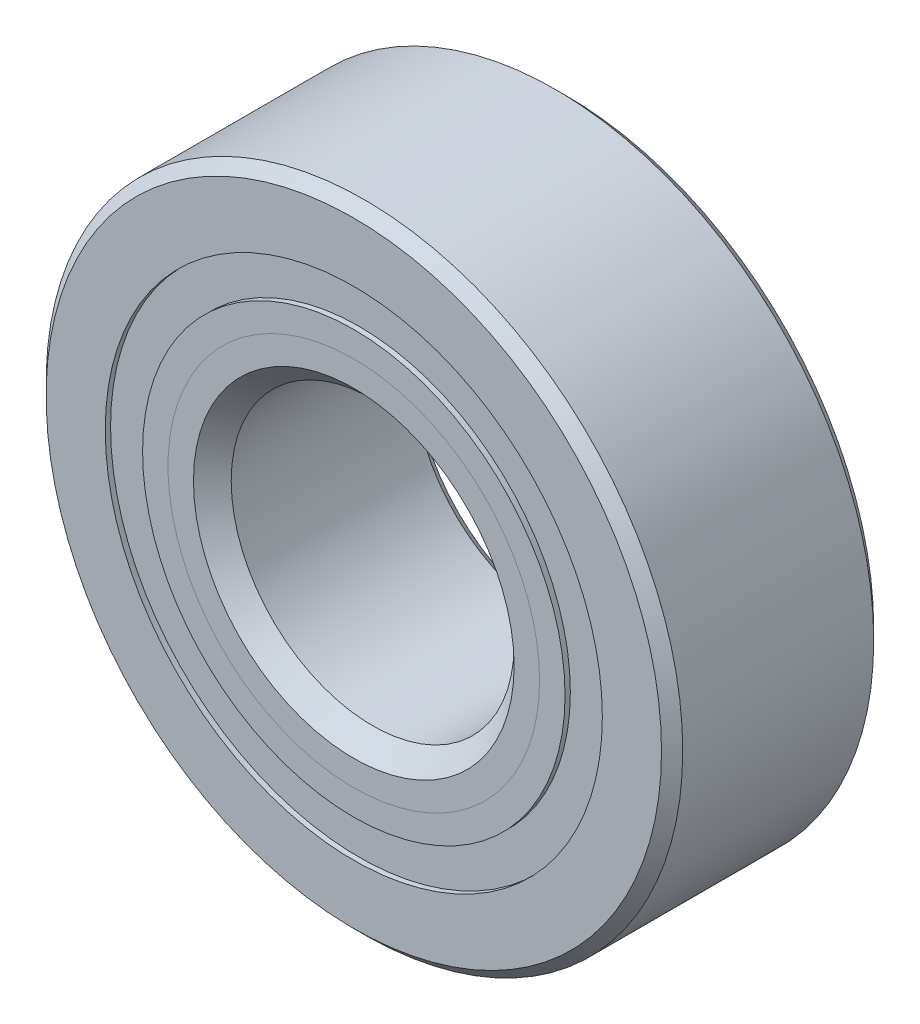
SolidWorks part; units mm, degrees
ref_plane "Front Plane" through (0, 0, 0) normal (0, 0, 1) x (1, 0, 0)
ref_plane "Top Plane" through (0, 0, 0) normal (0, 1, 0) x (1, 0, 0)
ref_plane "Right Plane" through (0, 0, 0) normal (1, 0, 0) x (0, 0, -1)
sketch "Sketch1" plane through (0, 0, 0) normal (1, 0, 0) x (0, 0, -1)
  line L0 (-4.7625, 0) -> (4.7625, 0) construction
  line L1 (0, 14.2875) -> (0, -14.2875) construction
  line L2 (4.2863, 14.2875) -> (-4.2863, 14.2875)
  line L3 (-4.2863, 14.2875) -> (-4.7625, 13.8113)
  line L4 (-4.7625, 13.8113) -> (-4.7625, 11.1561)
  line L5 (-4.7625, 11.1561) -> (-2.1167, 11.1561)
  line L6 (4.7625, 11.1561) -> (2.1167, 11.1561)
  line L7 (4.7625, 13.8113) -> (4.7625, 11.1561)
  line L8 (4.2863, 14.2875) -> (4.7625, 13.8113)
  line L9 (0, 14.2875) -> (0, 10.3187) construction
  line L10 (0, 10.3187) -> (0, 6.35) construction
  arc A0 (-2.1167, 11.1561) -> (2.1167, 11.1561) centre (0, 10.3187) cw
  point P14 (0, 6.35)
  dimension "Width" = 9.525
  dimension "OD" = 28.575
  dimension "D1" = 45
  dimension "D2" = 0.4763
  dimension "D3" = 4.2333
  dimension "D4" = 0.8374
revolve "Revolve1" add sketch "Sketch1" angle 360 about L0
sketch "Sketch2" plane through (0, 0, 0) normal (1, 0, 0) x (0, 0, -1)
  line L0 (-4.7625, 9.4814) -> (-2.1167, 9.4814)
  line L1 (-4.7625, 13.8113) -> (-4.7625, -13.8113) construction
  line L2 (-4.7625, 9.4814) -> (-4.7625, 8.3388)
  line L3 (-4.7625, 8.3388) -> (-3.6199, 7.1962)
  line L4 (-3.6199, 7.1962) -> (0, 7.1962)
  line L5 (0, 14.2875) -> (0, -14.2875) construction
  line L6 (0, 7.1962) -> (0, 8.0425)
  line L7 (0, 8.0425) -> (0, 6.35) construction
  line L8 (-4.7625, 9.4814) -> (-4.7625, 7.1962) construction
  line L9 (-4.7625, 7.1962) -> (-3.6199, 7.1962) construction
  arc A0 (-2.1167, 9.4814) -> (0, 8.0425) centre (0, 10.3187) ccw
  arc A1 (2.1167, 11.1561) -> (-2.1167, 11.1561) centre (0, 10.3187) ccw construction
  circle A2 centre (0, 10.3187) radius 2.2763 construction
  dimension "D1" = 45
revolve "Revolve2" add sketch "Sketch2" angle 360 about L0
sketch "Sketch3" plane through (0, 0, 0) normal (1, 0, 0) x (0, 0, -1)
  line L0 (-4.7625, 8.3388) -> (-3.6199, 7.1962)
  line L1 (-3.6199, 7.1962) -> (0, 7.1962)
  line L2 (0, 7.1962) -> (0, 8.0425)
  line L3 (-4.7625, 8.3388) -> (-4.7625, 7.1962)
  line L4 (-4.7625, 9.4814) -> (-4.7625, 7.1962) construction
  line L5 (-4.7625, 7.1962) -> (-3.9163, 6.35)
  line L6 (-3.9163, 6.35) -> (4.2863, 6.35)
  line L7 (4.2863, 14.2875) -> (4.2863, -14.2875) construction
  line L8 (4.2863, 6.35) -> (4.7625, 6.8262)
  line L9 (4.7625, -13.8113) -> (4.7625, 13.8113) construction
  line L10 (4.7625, 6.8262) -> (4.7625, 9.4814)
  line L11 (4.7625, 9.4814) -> (2.1167, 9.4814)
  line L13 (4.2863, 14.2875) -> (4.7625, 13.8113) construction
  circle A0 centre (0, 10.3187) radius 2.2763 construction
  arc A1 (2.1167, 9.4814) -> (0, 8.0425) centre (0, 10.3187) cw
revolve "Revolve3" add sketch "Sketch3" angle 360 about L0
sketch "Sketch4" plane through (0, 0, 0) normal (1, 0, 0) x (0, 0, -1)
  line L0 (-2.2763, 10.3187) -> (2.2763, 10.3187)
  circle A1 centre (0, 10.3187) radius 2.2763 construction
  arc A2 (-2.2763, 10.3187) -> (2.2763, 10.3187) centre (0, 10.3187) cw
  arc A3 (2.1167, 11.1561) -> (-2.1167, 11.1561) centre (0, 10.3187) ccw construction
revolve "Revolve4" add sketch "Sketch4" angle 360 about L0
ref_axis "Axis1" through (0, 0, -4.7625) along (0, 0, 1)
pattern_circular "CirPattern1" count 10 every 36 about axis through (0, 0, -4.7625) along (0, 0, 1) of bodies 104
sketch "Sketch5" plane through (0, 0, 0) normal (1, 0, 0) x (0, 0, -1)
  line L0 (-4.7625, 11.1561) -> (-2.1167, 11.1561) construction
  line L1 (-4.5244, 11.1561) -> (-2.2763, 11.1561)
  line L2 (-4.5244, 11.1561) -> (-4.5244, 9.4814)
  line L3 (-4.5244, 9.4814) -> (-2.2763, 9.4814)
  line L4 (-2.2763, 11.1561) -> (-2.2763, 9.4814)
  line L5 (-4.7625, 9.4814) -> (-2.1167, 9.4814) construction
  line L6 (-4.2863, 14.2875) -> (-4.7625, 13.8113) construction
  line L7 (0, 14.2875) -> (0, 6.35) construction
  line L8 (4.5244, 9.4814) -> (2.2763, 9.4814)
  line L9 (2.2763, 11.1561) -> (2.2763, 9.4814)
  line L10 (4.5244, 11.1561) -> (2.2763, 11.1561)
  line L11 (4.5244, 11.1561) -> (4.5244, 9.4814)
  circle A0 centre (0, 10.3187) radius 2.2763 construction
  point P10 (-4.5244, 14.0494)
revolve "Revolve5" add sketch "Sketch5" angle 360 about L0
equation "\"D2@Sketch1\" = \"Width@Sketch1\"*.05"
equation "\"D3@Sketch1\" = \"Width@Sketch1\"/2.25"
equation "\"D4@Sketch1\" = (((\"OD@Sketch1\"-\"Width@Sketch1\")/2)/3.25)/3.5"
equation "\"D2@CirPattern1\" = 360/\"Balls@CirPattern1\""
